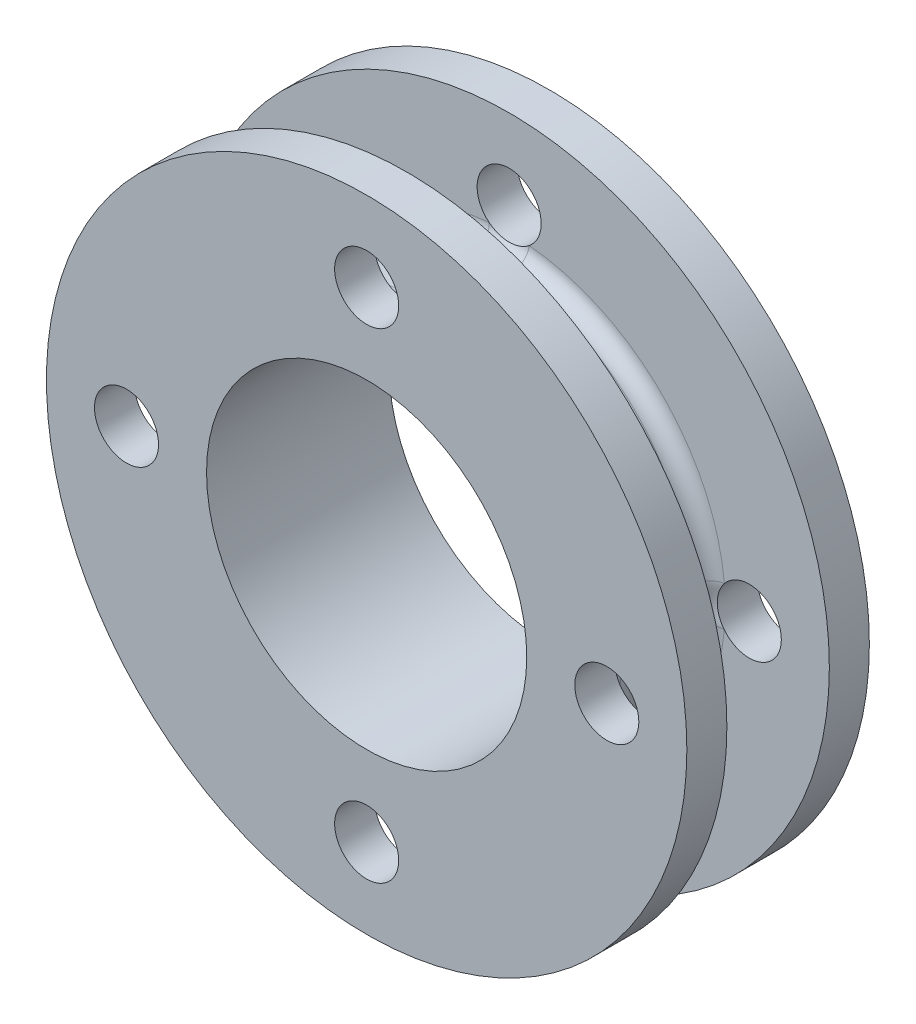
SolidWorks part; units mm, degrees
ref_plane "Plano frontal" through (0, 0, 0) normal (0, 0, 1) x (1, 0, 0)
ref_plane "Plano superior" through (0, 0, 0) normal (0, 1, 0) x (1, 0, 0)
ref_plane "Plano direito" through (0, 0, 0) normal (1, 0, 0) x (0, 0, -1)
sketch "Esboço1" plane through (0, 0, 0) normal (0, 0, 1) x (1, 0, 0)
  circle A0 centre (-15, 0) radius 2
  circle A1 centre (0, 0) radius 20
  circle A8 centre (0, -15) radius 2
  circle A14 centre (0, 0) radius 7.5 construction
  circle A15 centre (0, 0) radius 7.5 construction
  circle A16 centre (0, 0) radius 10
  circle A17 centre (0, 0) radius 15 construction
  circle A18 centre (0, 15) radius 2
  circle A19 centre (15, 0) radius 2
  point P11 (0, 0)
  dimension "D2" = 40
  dimension "D3" = 30
  dimension "D1" = 2.5
  dimension "D4" = 4
extrude "Ressalto-extrusão1" add sketch "Esboço1" along normal blind 2.5
sketch "Esboço2" plane through (0, 0, 2.5) normal (0, 0, 1) x (1, 0, 0)
  circle A0 centre (0, 0) radius 10 construction
  circle A1 centre (0, 0) radius 10
  circle A2 centre (0, 0) radius 12.5
  dimension "D1" = 2.5
extrude "Ressalto-extrusão2" add sketch "Esboço2" along normal up to surface (8.9 mm away)
sketch "Esboço3" plane through (0, 0, 11.4) normal (0, 0, 1) x (1, 0, 0)
  circle A0 centre (0, 0) radius 20 construction
  circle A1 centre (0, 0) radius 20
  circle A2 centre (-15, 0) radius 2
  circle A3 centre (0, -15) radius 2 construction
  circle A4 centre (0, 15) radius 2
  circle A5 centre (15, 0) radius 2
  circle A7 centre (0, 0) radius 20
  circle A8 centre (0, 0) radius 10 construction
  circle A10 centre (0, -15) radius 2
  circle A14 centre (0, -15) radius 2
  circle A15 centre (0, 0) radius 10
  circle A16 centre (0, 0) radius 20
  point P14 (0, 0)
  circle M3 centre (0, 0) radius 12.5
  dimension "D2" = 0
  dimension "D1" = 4
extrude "Ressalto-extrusão3" add sketch "Esboço3" against normal blind 2.5 contours A1 A10 A5 A4 A2 M3 region at (-19.4343, 0, 11.4)
fillet "Filete1" radius 1 2 edges at (12.5, 0, 8.9) (12.5, 0, 2.5)
